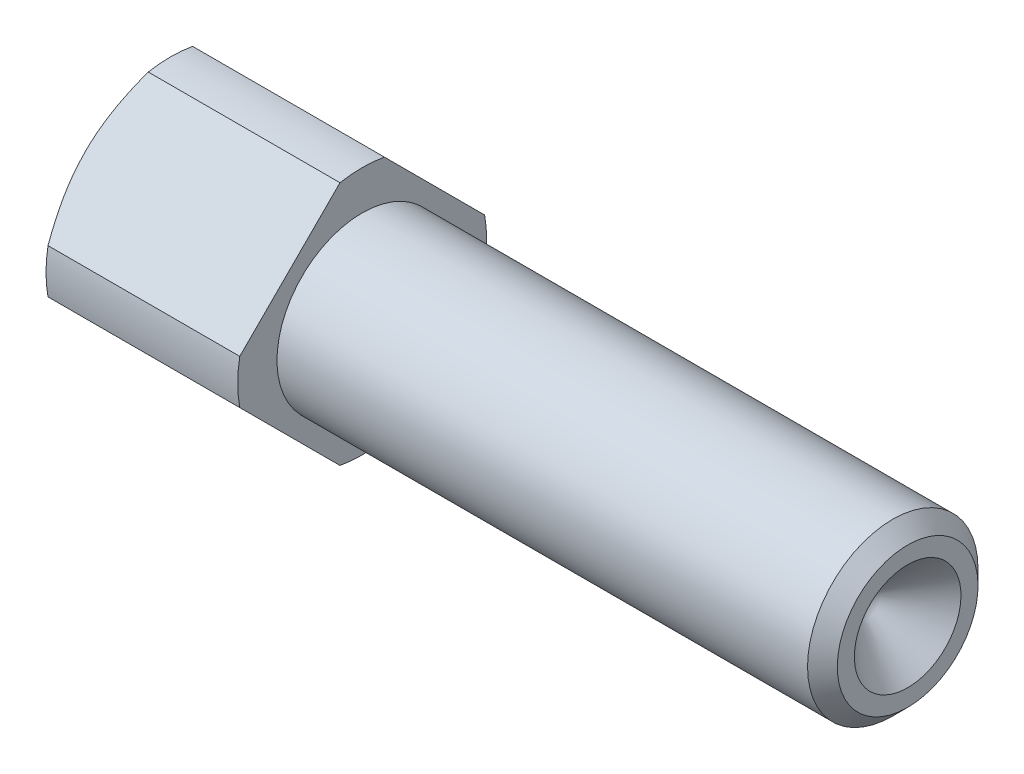
SolidWorks part; units mm, degrees
ref_plane "Front" through (0, 0, 0) normal (0, 0, 1) x (1, 0, 0)
ref_plane "Top" through (0, 0, 0) normal (0, 1, 0) x (1, 0, 0)
ref_plane "Right" through (0, 0, 0) normal (1, 0, 0) x (0, 0, -1)
sketch "Sketch1" plane through (0, 0, 0) normal (1, 0, 0) x (0, 0, -1)
  circle A0 centre (0, 0) radius 3.65
extrude "BaseHead" add sketch "Sketch1" along normal blind 6
sketch "Sketch2" plane through (0, -2.2415, -0.2463) normal (-1, 0, 0) x (0, 0, 1)
  line L1 (4.4889, 2.2415) -> (0.2463, 6.4841)
  line L2 (0.2463, 6.4841) -> (-3.9963, 2.2415)
  line L3 (-3.9963, 2.2415) -> (0.2463, -2.0012)
  line L4 (0.2463, -2.0012) -> (4.4889, 2.2415)
  circle A0 centre (0.2463, 2.2415) radius 3 construction
extrude "Cut-Extrude1" cut sketch "Sketch2" against normal blind 6 flip side to cut
sketch "Sketch3" plane through (1.2597, -5.2747, 0) normal (0, 0, 1) x (0, -1, 0)
  line L0 (-9.2897, -1.2597) -> (-8.2747, -1.2597)
  line L2 (-8.2747, -1.2597) -> (-9.2897, -0.6737)
  line L3 (-9.2897, -0.6737) -> (-9.2897, -1.2597)
  line L4 (-5.2747, 0.2856) -> (-5.2747, -6.82) construction
  line L6 (-8.8662, -1.2597) -> (-5.9259, -1.2597) construction
  dimension "D1" = 8.03
revolve "Cut-Revolve1" cut sketch "Sketch3" angle 360 about L4
sketch "Sketch4" plane through (-10.3472, 12.8472, 0) normal (0, 0, 1) x (0, -1, 0)
  line L0 (12.8472, 16.3472) -> (15.3472, 16.3472)
  line L1 (15.3472, 32.3472) -> (14.4106, 32.3472)
  line L2 (15.3472, 16.3472) -> (15.3472, 32.3472)
  line L3 (14.4106, 32.3472) -> (12.8472, 30.7839)
  line L4 (9.2558, 16.3472) -> (12.196, 16.3472) construction
  line L5 (12.8472, 30.7839) -> (12.8472, 16.3472)
  line L6 (12.8472, 24.434) -> (12.8472, -1.2396) construction
  dimension "l" = 16
  dimension "D1" = 45
revolve "BaseBody" add sketch "Sketch4" angle 360 about L6
cosmetic thread "ThreadCosmetic1" [suppressed] parameters "D1"=6, "d"=4
fillet "HeadFillet" [suppressed] radius 0.2
chamfer "Chamfer1" distance 0.4367 angle 45 1 edges at (22, 2.5, 0)
sketch "Sketch8" plane through (0, 0, 0) normal (0, 0, 1) x (1, 0, 0)
  line L0 (16, 2.067) -> (16.25, 2.5)
  line L1 (16.25, 2.5) -> (16.25, 3)
  line L2 (16.25, 3) -> (15.75, 3)
  line L3 (15.75, 3) -> (15.75, 2.5)
  line L4 (15.75, 2.5) -> (16, 2.067)
  line L5 (0, 0) -> (18.2989, 0) construction
  line L6 (0, 2.1213) -> (0, -2.1213) construction
  line L7 (22, -2.0633) -> (22, 2.0633) construction
  dimension "D1" = 5
  dimension "D3" = 6
revolve "Cut-Revolve10" [suppressed] cut sketch "Sketch8" angle 360 about L5
pattern_linear "LPattern10" [suppressed] count 10 spacing 0.6 along (1, 0, 0) of bodies 105
equation "\"d2@Sketch3\" = \"s@Sketch2\""
equation "\"D1@Sketch3\" = \"e@Sketch1\" * 1.1"
equation "\"k+c@BaseHead\" = \"k@Cut-Extrude1\""
equation "\"D1@Chamfer1\" = \"d@Sketch4\" / 2 - \"dz@Sketch4\" / 2-0.5"
equation "\"D1@Sketch8\" = \"d@Sketch4\""
equation "\"D3@Sketch8\" = \"D1@ThreadCosmetic1\""
equation "\"ss@Sketch8\" =  ( \"d@Sketch4\" - \"d@ThreadCosmetic1\" )  / 2"
equation "\"D3@LPattern10\" = \"ss@Sketch8\" * 1.2"
equation "\"D1@LPattern10\" = \"D1@ThreadCosmetic1\" / \"D3@LPattern10\""
